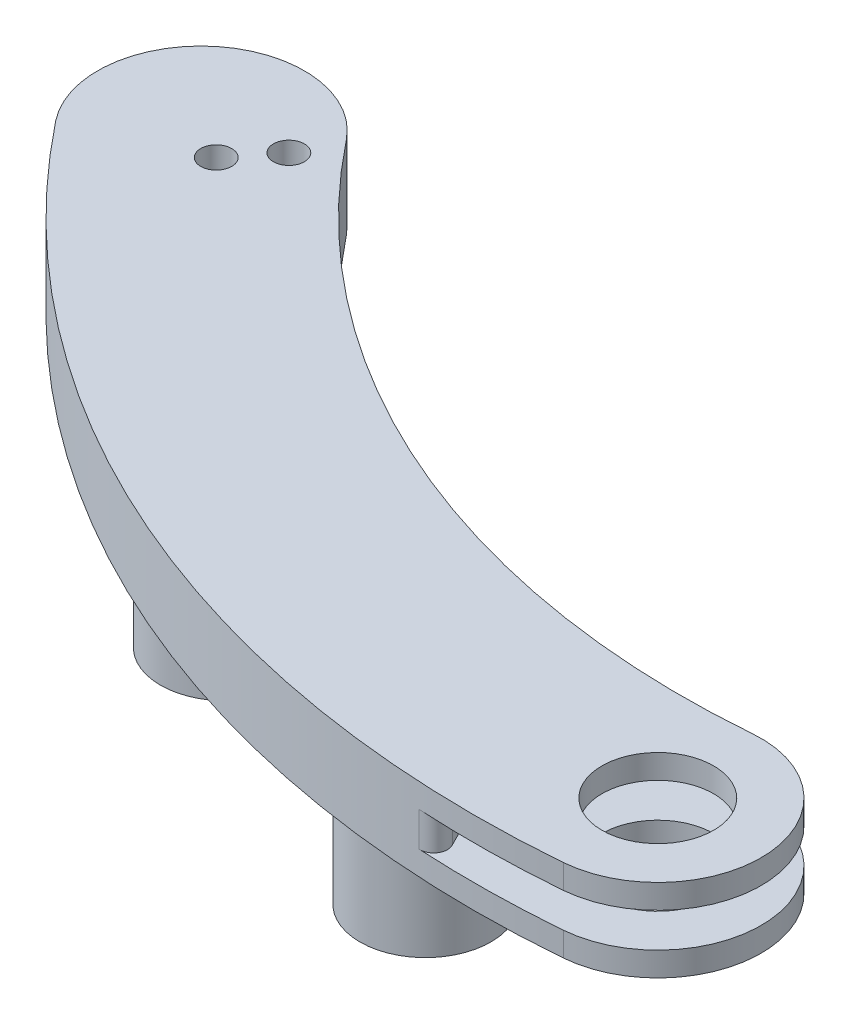
SolidWorks part; units mm, degrees
ref_plane "Front Plane" through (0, 0, 0) normal (0, 0, 1) x (1, 0, 0)
ref_plane "Top Plane" through (0, 0, 0) normal (0, 1, 0) x (1, 0, 0)
ref_plane "Right Plane" through (0, 0, 0) normal (1, 0, 0) x (0, 0, -1)
sketch "Sketch1" plane through (0, 0, 0) normal (0, 1, 0) x (1, 0, 0)
  arc A0 (0, 0) -> (-117, 50.7404) centre (-11.1561, 134.5383) cw construction
  arc A1 (-128.7604, 41.4296) -> (1.2396, -14.9487) centre (-11.1561, 134.5383) ccw
  arc A2 (-105.2396, 60.0513) -> (-1.2396, 14.9487) centre (-11.1561, 134.5383) ccw
  arc A3 (-105.2396, 60.0513) -> (-128.7604, 41.4296) centre (-117, 50.7404) ccw
  arc A4 (1.2396, -14.9487) -> (-1.2396, 14.9487) centre (0, 0) ccw
  arc A5 (-16.6792, 14.6654) -> (-15.4249, -15.401) centre (4.9458, 0.5082) ccw
  point P3 (-64.8692, 10.6839)
  dimension "D3" = 30
  dimension "D4" = 150
  dimension "D1" = 75
  dimension "D2" = 130
extrude "Boss-Extrude4" add sketch "Sketch1" along normal blind 12 contours A5 A2 A3 A1 region at (-76.6272, 0, -21.3687)
extrude "Boss-Extrude5" add sketch "Sketch1<6>" along normal blind 3.5 contours A2 A5 A1 A4 region at (-3.6374, 0, 0.1249)
sketch "Sketch1<6>" plane through (0, 0, 0) normal (0, 1, 0) x (1, 0, 0) same geometry as "Sketch1"
extrude "Boss-Extrude6" add sketch "Sketch1<8>" along normal blind 12 contours A2 A5 A1 A4 region at (-3.6374, 0, 0.1249)
sketch "Sketch1<8>" plane through (0, 0, 0) normal (0, 1, 0) x (1, 0, 0) same geometry as "Sketch1"
extrude "Cut-Extrude2" cut sketch "Sketch1<9>" along normal blind 8.5 contours A2 A5 A1 A4 region at (-3.6374, 0, 0.1249)
sketch "Sketch1<9>" plane through (0, 0, 0) normal (0, 1, 0) x (1, 0, 0) same geometry as "Sketch1"
extrude "Boss-Extrude7" add sketch "Sketch1<10>" along normal blind 3.5 contours A2 A5 A1 A4 region at (-3.6374, 0, 0.1249)
sketch "Sketch1<10>" plane through (0, 0, 0) normal (0, 1, 0) x (1, 0, 0) same geometry as "Sketch1"
sketch "Sketch2" plane through (0, 12, 0) normal (0, 1, 0) x (1, 0, 0)
  circle A0 centre (0, 0) radius 8.1
  dimension "D1" = 16.2
extrude "Cut-Extrude3" cut sketch "Sketch2" against normal blind 12
fillet "Fillet1" radius 5 1 edges at (-16.6792, 6, -14.6654)
fillet "Fillet2" radius 2 1 edges at (-15.4249, 6, 15.401)
sketch "Sketch3" plane through (0, 12, 0) normal (0, 1, 0) x (1, 0, 0)
  circle A0 centre (-107.8166, 54.3025) radius 2.25
  circle A1 centre (-112.4991, 48.4438) radius 2.25
  dimension "D1" = 4.5
  dimension "D2" = 4.5
  dimension "D3" = 7.5
  dimension "D4" = 6.3
extrude "Cut-Extrude4" cut sketch "Sketch3" against normal blind 12
sketch "Sketch4" plane through (0, 0, 0) normal (0, 1, 0) x (1, 0, 0)
  circle A0 centre (-35.5199, 1.812) radius 8.1
  circle A1 centre (-35.5199, 1.812) radius 9.5
  circle A2 centre (-82.2472, 19.6043) radius 8.1
  circle A3 centre (-82.2472, 19.6043) radius 9.5
  dimension "D1" = 16.2
  dimension "D2" = 19
  dimension "D3" = 50
extrude "Boss-Extrude8" add sketch "Sketch4" against normal blind 20
